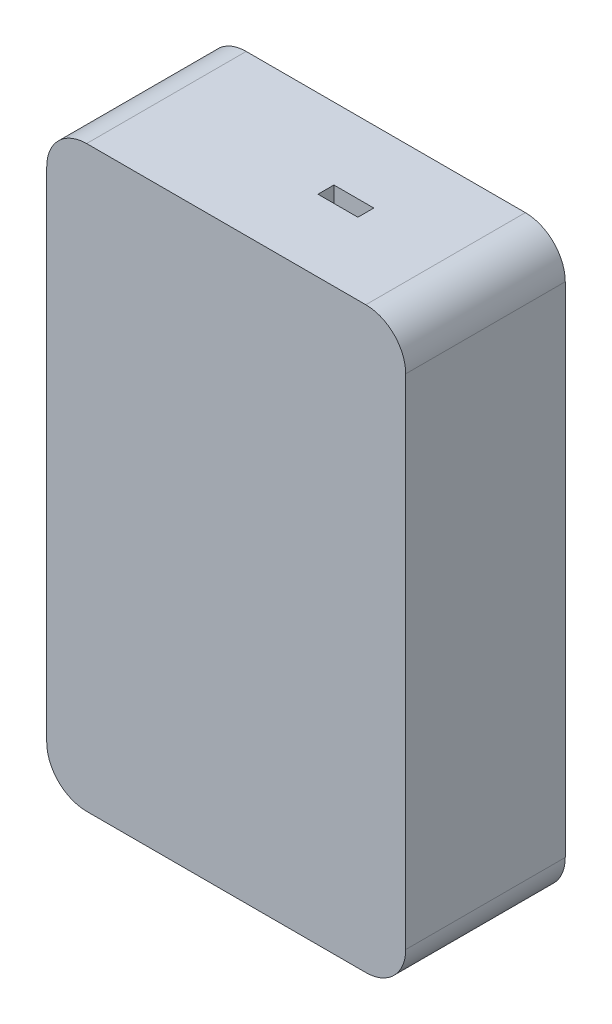
SolidWorks part; units mm, degrees
ref_plane "Front Plane" through (0, 0, 0) normal (0, 0, 1) x (1, 0, 0)
ref_plane "Top Plane" through (0, 0, 0) normal (0, 1, 0) x (1, 0, 0)
ref_plane "Right Plane" through (0, 0, 0) normal (1, 0, 0) x (0, 0, -1)
sketch "Sketch1" plane through (0, 0, 0) normal (0, 1, 0) x (1, 0, 0)
  line L0 (-45, 20) -> (45, 20)
  line L1 (-37.5, -12.5) -> (37.5, -12.5)
  line L2 (-37.5, -12.5) -> (-37.5, 12.5)
  line L3 (-37.5, 12.5) -> (37.5, 12.5)
  line L4 (37.5, -12.5) -> (37.5, 12.5)
  line L5 (-37.5, -12.5) -> (37.5, 12.5) construction
  line L6 (-37.5, 12.5) -> (37.5, -12.5) construction
  line L7 (45, -20) -> (45, 20)
  line L8 (-45, -20) -> (45, -20)
  line L9 (-45, -20) -> (-45, 20)
  point P0 (0, 0)
  dimension "D1" = 25
  dimension "D2" = 75
  dimension "D3" = 7.5
extrude "Boss-Extrude2" add sketch "Sketch1" along normal blind 65 and the other way blind 65
sketch "Sketch2" plane through (0, -65, 0) normal (0, -1, 0) x (1, 0, 0)
  line L1 (-45, -20) -> (45, -20)
  line L2 (-45, -20) -> (-45, 20)
  line L3 (-45, 20) -> (45, 20)
  line L4 (45, -20) -> (45, 20)
  line L5 (-45, -20) -> (45, 20) construction
  line L6 (-45, 20) -> (45, -20) construction
  point P0 (0, 0)
  point P7 (-45, 17.5)
extrude "Boss-Extrude3" add sketch "Sketch2" along normal blind 7.5
mirror "Mirror1" about plane through (0, 0, 0) normal (0, 1, 0) of "Boss-Extrude3"
sketch "Sketch3" plane through (0, -72.5, 0) normal (0, -1, 0) x (1, 0, 0)
  circle A0 centre (-20, 0) radius 6.5
  point P2 (-29.0453, -3.4409)
  point P4 (0, 0)
  point P6 (-19.4439, 0)
  dimension "D1" = 13
  dimension "D2" = 20
extrude "Cut-Extrude1" cut sketch "Sketch3" against normal up to next
sketch "Sketch6" plane through (0, 0, 0) normal (0, 0, 1) x (1, 0, 0)
  line L0 (-37.5, -65) -> (-37.5, 65) construction
  line L1 (-35, -7.5) -> (35, -7.5)
  line L2 (-35, -7.5) -> (-35, 62.5)
  line L3 (-35, 62.5) -> (35, 62.5)
  line L4 (35, -7.5) -> (35, 62.5)
  line L5 (-35, -7.5) -> (35, 62.5) construction
  line L6 (-35, 62.5) -> (35, -7.5) construction
  line L7 (37.5, 65) -> (-37.5, 65) construction
  line L8 (37.5, -65) -> (-37.5, -65) construction
  line L9 (-35, -62.5) -> (19.7, -62.5)
  line L10 (-35, -62.5) -> (-35, -21.5)
  line L11 (-35, -21.5) -> (19.7, -21.5)
  line L12 (19.7, -62.5) -> (19.7, -21.5)
  line L13 (-35, -62.5) -> (19.7, -21.5) construction
  line L14 (-35, -21.5) -> (19.7, -62.5) construction
  point P0 (0, 27.5)
  point P5 (0, 0)
  point P7 (-7.65, -42)
  dimension "D1" = 70
  dimension "D2" = 70
  dimension "D3" = 2.5
  dimension "D4" = 41
  dimension "D5" = 54.7
  dimension "D6" = 2.5
  dimension "D7" = 2.5
extrude "Boss-Extrude4" add sketch "Sketch6" along normal blind 10 and the other way blind 10
sketch "Sketch7" plane through (0, 0, 0) normal (0, 0, 1) x (1, 0, 0)
  line L0 (-37.5, -65) -> (-37.5, 65) construction
  line L1 (-37.5, -19) -> (27.5, -19)
  line L2 (-37.5, -19) -> (-37.5, -10)
  line L3 (-37.5, -10) -> (27.5, -10)
  line L4 (27.5, -19) -> (27.5, -10)
  line L5 (37.5, -65) -> (37.5, 65) construction
  line L8 (-35, -7.5) -> (35, -7.5) construction
  dimension "D1" = 10
  dimension "D2" = 9
  dimension "D3" = 2.5
extrude "Boss-Extrude5" add sketch "Sketch7" along normal up to next and the other way up to next
sketch "Sketch9" plane through (0, 0, 0) normal (0, 0, 1) x (1, 0, 0)
  line L0 (-45, 72.5) -> (45, 72.5) construction
  line L1 (5, 72.5) -> (15, 72.5)
  line L2 (5, 72.5) -> (5, 65)
  line L3 (5, 65) -> (15, 65)
  line L4 (15, 72.5) -> (15, 65)
  line L5 (37.5, 65) -> (-37.5, 65) construction
  line L6 (-35, 62.5) -> (-35, -7.5) construction
  line L7 (-45, -72.5) -> (-45, 72.5) construction
  line L8 (-45, 0) -> (-37.5, 0)
  line L9 (-45, 0) -> (-45, 10)
  line L10 (-45, 10) -> (-37.5, 10)
  line L11 (-37.5, 0) -> (-37.5, 10)
  line L12 (-37.5, -10) -> (-37.5, 65) construction
  point P18 (0, 0)
  dimension "D1" = 10
  dimension "D2" = 40
  dimension "D3" = 10
extrude "Cut-Extrude2" cut sketch "Sketch9" against normal blind 2 and the other way blind 2
fillet "Fillet1" radius 10 4 edges at (-45, 72.5, 0) (-45, -72.5, 0) (45, -72.5, 0) (45, 72.5, 0)
fillet "Fillet2" radius 3 2 edges at (27.5, -19, 0) (27.5, -10, 0)
